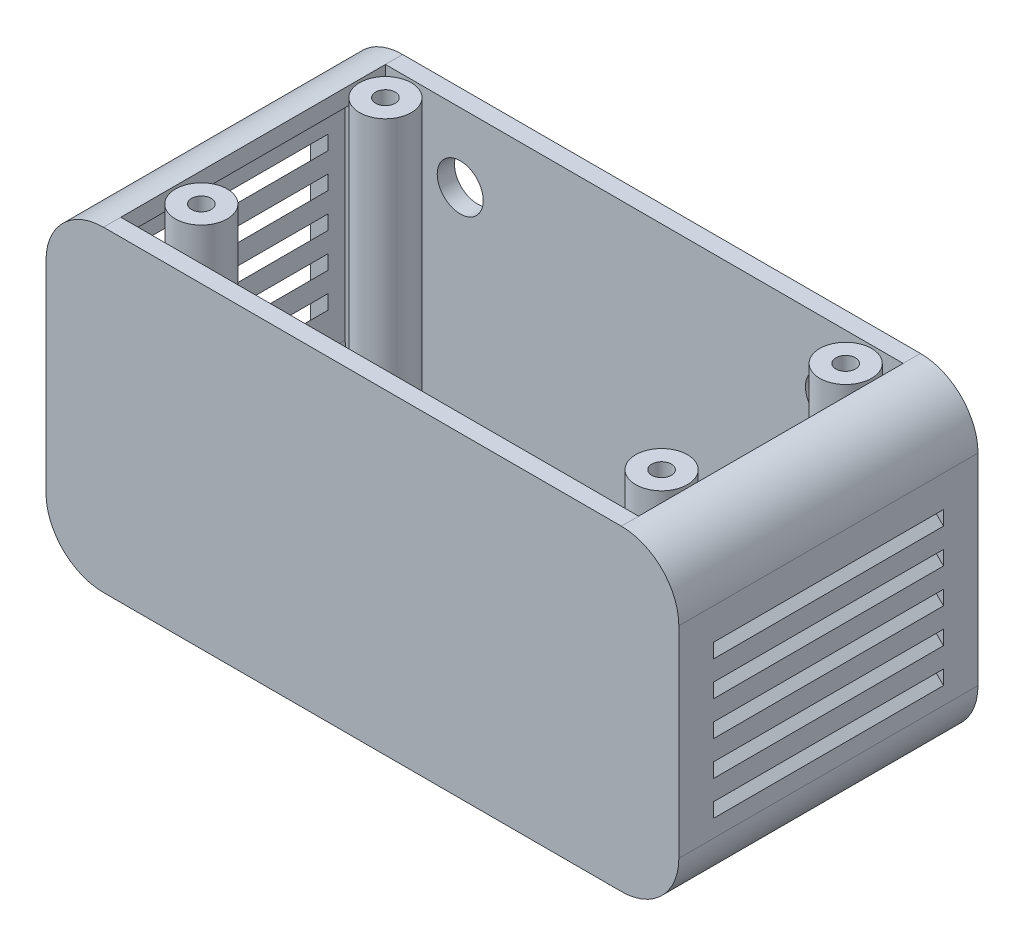
SolidWorks part; units mm, degrees
material "ABS"
ref_plane "Front Plane" through (0, 0, 0) normal (0, 0, 1) x (1, 0, 0)
ref_plane "Top Plane" through (0, 0, 0) normal (0, 1, 0) x (1, 0, 0)
ref_plane "Right Plane" through (0, 0, 0) normal (1, 0, 0) x (0, 0, -1)
sketch "Sketch1" plane through (0, 0, 0) normal (0, 0, 1) x (1, 0, 0)
  line L0 (-45, -55) -> (45, -55)
  line L1 (55, -45) -> (55, -10)
  line L2 (45, 0) -> (-45, 0)
  line L3 (-55, -10) -> (-55, -45)
  arc A0 (45, -55) -> (55, -45) centre (45, -45) ccw
  arc A1 (55, -10) -> (45, 0) centre (45, -10) ccw
  arc A2 (-45, 0) -> (-55, -10) centre (-45, -10) ccw
  arc A3 (-55, -45) -> (-45, -55) centre (-45, -45) ccw
extrude "Boss-Extrude1" add sketch "Sketch1" along normal blind 52
shell "Shell1" thickness 3 removed face at (0, 0, 26)
sketch "Sketch2" plane through (0, 0, 0) normal (0, 1, 0) x (1, 0, 0)
  circle A0 centre (-40, -8) radius 4.5
  circle A1 centre (40, -8) radius 4.5
  circle A2 centre (-40, -40) radius 4.5
  circle A3 centre (40, -40) radius 4.5
extrude "Boss-Extrude2" add sketch "Sketch2" against normal blind 52
sketch "Sketch3" plane through (0, -55, 0) normal (0, -1, 0) x (1, 0, 0)
  circle A0 centre (-40, 8) radius 3.25
  circle A1 centre (40, 8) radius 3.25
  circle A2 centre (-40, 40) radius 3.25
  circle A3 centre (40, 40) radius 3.25
extrude "Cut-Extrude1" cut sketch "Sketch3" against normal blind 49
sketch "Sketch4" plane through (0, -6, 0) normal (0, -1, 0) x (1, 0, 0)
  circle A0 centre (-40, 8) radius 1.7
  circle A1 centre (40, 8) radius 1.7
  circle A2 centre (-40, 40) radius 1.7
  circle A3 centre (40, 40) radius 1.7
extrude "Cut-Extrude2" cut sketch "Sketch4" against normal through all
ref_plane "Plane1" through (0, 0, 26) normal (0, 0, 1) x (1, 0, 0)
sketch "Sketch5" plane through (0, 0, 26) normal (0, 0, 1) x (1, 0, 0)
  line L0 (-51, -14) -> (-51, -11.5)
  line L1 (-51, -11.5) -> (-55.5, -16)
  line L2 (-55.5, -16) -> (-55.5, -18.5)
  line L3 (-55.5, -18.5) -> (-51, -14)
  line L4 (51, -14) -> (51, -11.5)
  line L5 (51, -11.5) -> (55.5, -16)
  line L6 (55.5, -16) -> (55.5, -18.5)
  line L7 (55.5, -18.5) -> (51, -14)
  line L8 (-51, -20) -> (-51, -17.5)
  line L9 (-51, -17.5) -> (-55.5, -22)
  line L10 (-55.5, -22) -> (-55.5, -24.5)
  line L11 (-55.5, -24.5) -> (-51, -20)
  line L12 (51, -20) -> (51, -17.5)
  line L13 (51, -17.5) -> (55.5, -22)
  line L14 (55.5, -22) -> (55.5, -24.5)
  line L15 (55.5, -24.5) -> (51, -20)
  line L16 (-51, -26) -> (-51, -23.5)
  line L17 (-51, -23.5) -> (-55.5, -28)
  line L18 (-55.5, -28) -> (-55.5, -30.5)
  line L19 (-55.5, -30.5) -> (-51, -26)
  line L20 (51, -26) -> (51, -23.5)
  line L21 (51, -23.5) -> (55.5, -28)
  line L22 (55.5, -28) -> (55.5, -30.5)
  line L23 (55.5, -30.5) -> (51, -26)
  line L24 (-51, -32) -> (-51, -29.5)
  line L25 (-51, -29.5) -> (-55.5, -34)
  line L26 (-55.5, -34) -> (-55.5, -36.5)
  line L27 (-55.5, -36.5) -> (-51, -32)
  line L28 (51, -32) -> (51, -29.5)
  line L29 (51, -29.5) -> (55.5, -34)
  line L30 (55.5, -34) -> (55.5, -36.5)
  line L31 (55.5, -36.5) -> (51, -32)
  line L32 (-51, -38) -> (-51, -35.5)
  line L33 (-51, -35.5) -> (-55.5, -40)
  line L34 (-55.5, -40) -> (-55.5, -42.5)
  line L35 (-55.5, -42.5) -> (-51, -38)
  line L36 (51, -38) -> (51, -35.5)
  line L37 (51, -35.5) -> (55.5, -40)
  line L38 (55.5, -40) -> (55.5, -42.5)
  line L39 (55.5, -42.5) -> (51, -38)
extrude "Cut-Extrude3" cut sketch "Sketch5" against normal blind 20 and the other way blind 20
sketch "Sketch6" plane through (0, -55, 0) normal (0, -1, 0) x (1, 0, 0)
  line L0 (-33, 12) -> (-33, 40) construction
  line L1 (-34.5, 12) -> (-34.5, 40)
  line L2 (-31.5, 12) -> (-31.5, 40)
  line L3 (-27, 12) -> (-27, 40) construction
  line L4 (-28.5, 12) -> (-28.5, 40)
  line L5 (-25.5, 12) -> (-25.5, 40)
  line L6 (-21, 12) -> (-21, 40) construction
  line L7 (-22.5, 12) -> (-22.5, 40)
  line L8 (-19.5, 12) -> (-19.5, 40)
  line L9 (-15, 12) -> (-15, 40) construction
  line L10 (-16.5, 12) -> (-16.5, 40)
  line L11 (-13.5, 12) -> (-13.5, 40)
  line L12 (-9, 12) -> (-9, 40) construction
  line L13 (-10.5, 12) -> (-10.5, 40)
  line L14 (-7.5, 12) -> (-7.5, 40)
  line L15 (-3, 12) -> (-3, 40) construction
  line L16 (-4.5, 12) -> (-4.5, 40)
  line L17 (-1.5, 12) -> (-1.5, 40)
  line L18 (3, 12) -> (3, 40) construction
  line L19 (1.5, 12) -> (1.5, 40)
  line L20 (4.5, 12) -> (4.5, 40)
  line L21 (9, 12) -> (9, 40) construction
  line L22 (7.5, 12) -> (7.5, 40)
  line L23 (10.5, 12) -> (10.5, 40)
  line L24 (33, 12) -> (33, 40) construction
  line L25 (31.5, 12) -> (31.5, 40)
  line L26 (34.5, 12) -> (34.5, 40)
  arc A0 (-34.5, 12) -> (-31.5, 12) centre (-33, 12) ccw
  arc A1 (-31.5, 40) -> (-34.5, 40) centre (-33, 40) ccw
  arc A2 (-28.5, 12) -> (-25.5, 12) centre (-27, 12) ccw
  arc A3 (-25.5, 40) -> (-28.5, 40) centre (-27, 40) ccw
  arc A4 (-22.5, 12) -> (-19.5, 12) centre (-21, 12) ccw
  arc A5 (-19.5, 40) -> (-22.5, 40) centre (-21, 40) ccw
  arc A6 (-16.5, 12) -> (-13.5, 12) centre (-15, 12) ccw
  arc A7 (-13.5, 40) -> (-16.5, 40) centre (-15, 40) ccw
  arc A8 (-10.5, 12) -> (-7.5, 12) centre (-9, 12) ccw
  arc A9 (-7.5, 40) -> (-10.5, 40) centre (-9, 40) ccw
  arc A10 (-4.5, 12) -> (-1.5, 12) centre (-3, 12) ccw
  arc A11 (-1.5, 40) -> (-4.5, 40) centre (-3, 40) ccw
  arc A12 (1.5, 12) -> (4.5, 12) centre (3, 12) ccw
  arc A13 (4.5, 40) -> (1.5, 40) centre (3, 40) ccw
  arc A14 (7.5, 12) -> (10.5, 12) centre (9, 12) ccw
  arc A15 (10.5, 40) -> (7.5, 40) centre (9, 40) ccw
  arc A16 (31.5, 12) -> (34.5, 12) centre (33, 12) ccw
  arc A17 (34.5, 40) -> (31.5, 40) centre (33, 40) ccw
  point P2 (-33, 26)
  point P7 (-27, 26)
  point P14 (-21, 26)
  point P21 (-15, 26)
  point P28 (-9, 26)
  point P35 (-3, 26)
  point P42 (3, 26)
  point P49 (9, 26)
  point P56 (33, 26)
extrude "Cut-Extrude4" cut sketch "Sketch6" against normal blind 3.5
sketch "Sketch7" plane through (0, 0, 0) normal (0, 0, -1) x (-1, 0, 0)
  circle A0 centre (32, -12) radius 4
  circle A1 centre (-32, -12) radius 4
extrude "Cut-Extrude5" cut sketch "Sketch7" against normal blind 3.5
sketch "Sketch8" plane through (0, -52, 0) normal (0, 1, 0) x (1, 0, 0)
  line L0 (-30.25, -26) -> (30.25, -26) construction
  line L1 (-47, -36) -> (-41, -36)
  line L2 (-47, -36) -> (-47, -16)
  line L3 (-47, -16) -> (-41, -16)
  line L4 (-41, -36) -> (-41, -16)
  line L5 (-47, -36) -> (-41, -16) construction
  line L6 (-47, -16) -> (-41, -36) construction
  point P0 (-44, -26)
extrude "Boss-Extrude3" add sketch "Sketch8" along normal blind 8
sketch "Sketch9" plane through (0, -44, 0) normal (0, 1, 0) x (1, 0, 0)
  line L0 (-30.25, -26) -> (30.25, -26) construction
  line L1 (-44.95, -34.3) -> (-43.05, -34.3)
  line L2 (-44.95, -34.3) -> (-44.95, -17.7)
  line L3 (-44.95, -17.7) -> (-43.05, -17.7)
  line L4 (-43.05, -34.3) -> (-43.05, -17.7)
  line L5 (-44.95, -34.3) -> (-43.05, -17.7) construction
  line L6 (-44.95, -17.7) -> (-43.05, -34.3) construction
  point P0 (-44, -26)
extrude "Cut-Extrude6" cut sketch "Sketch9" against normal blind 6
sketch "Sketch10" plane through (0, -55, 0) normal (0, -1, 0) x (1, 0, 0)
  circle A0 centre (20, 26) radius 5
extrude "Cut-Extrude7" cut sketch "Sketch10" against normal blind 3.5
